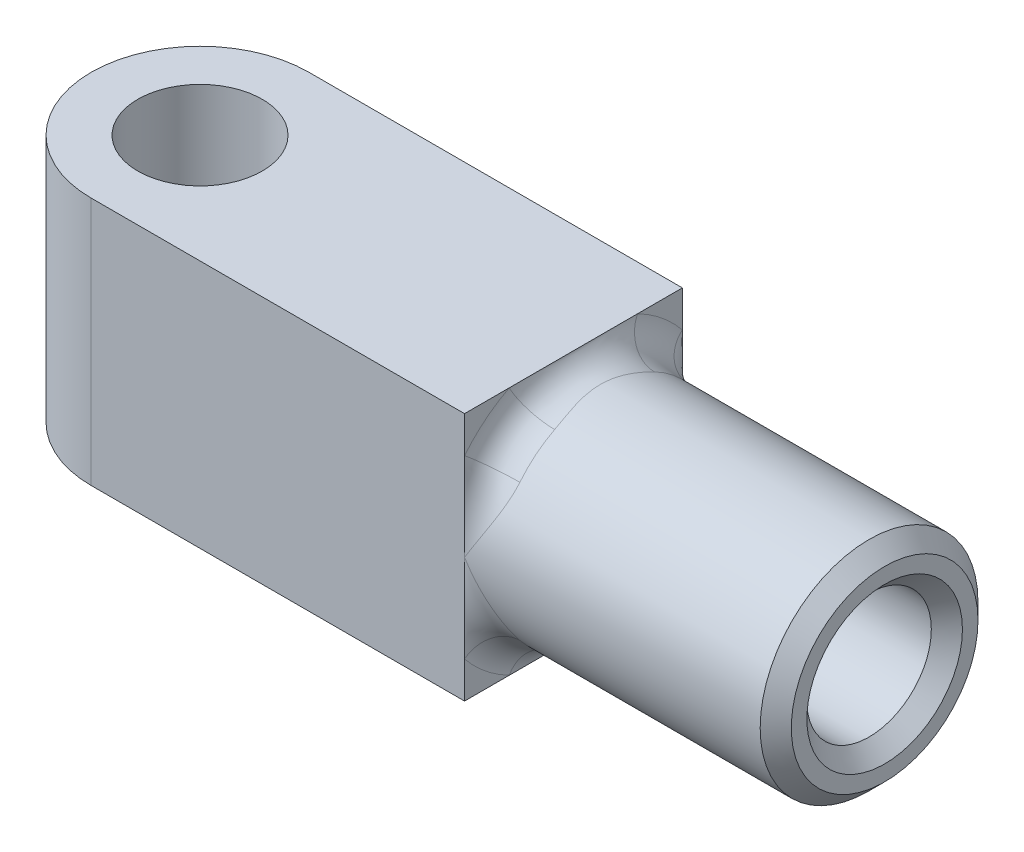
SolidWorks part; units mm, degrees
ref_plane "Front Plane" through (0, 0, 0) normal (0, 0, 1) x (1, 0, 0)
ref_plane "Top Plane" through (0, 0, 0) normal (0, 1, 0) x (1, 0, 0)
ref_plane "Right Plane" through (0, 0, 0) normal (1, 0, 0) x (0, 0, -1)
sketch "Sketch1" plane through (0, 0, 0) normal (0, 1, 0) x (1, 0, 0)
  line L1 (6, -3.5) -> (-6, -3.5)
  line L2 (6, -3.5) -> (6, 3.5)
  line L3 (6, 3.5) -> (-6, 3.5)
  circle A0 centre (-6, 0) radius 2
  arc A1 (-6, 3.5) -> (-6, -3.5) centre (-6, 0) ccw
  point P0 (6, 0)
  point P8 (0, 0)
  dimension "D3" = 4
  dimension "D1" = 3.5
extrude "Boss-Extrude1" add sketch "Sketch1" along normal mid plane 8
sketch "Sketch3" plane through (6, 0, 0) normal (1, 0, 0) x (0, 0, -1)
  circle A0 centre (0, 0) radius 3.5
  circle A1 centre (0, 0) radius 2
  dimension "D1" = 7
  dimension "D2" = 4
extrude "Boss-Extrude2" add sketch "Sketch3" along normal blind 10
fillet "Fillet1" radius 1 2 edges at (6, -3.5, 0) (6, 3.5, 0)
chamfer "Chamfer1" distance 0.5 angle 45 2 edges at (16, 0, -2) (16, 0, -3.5)
